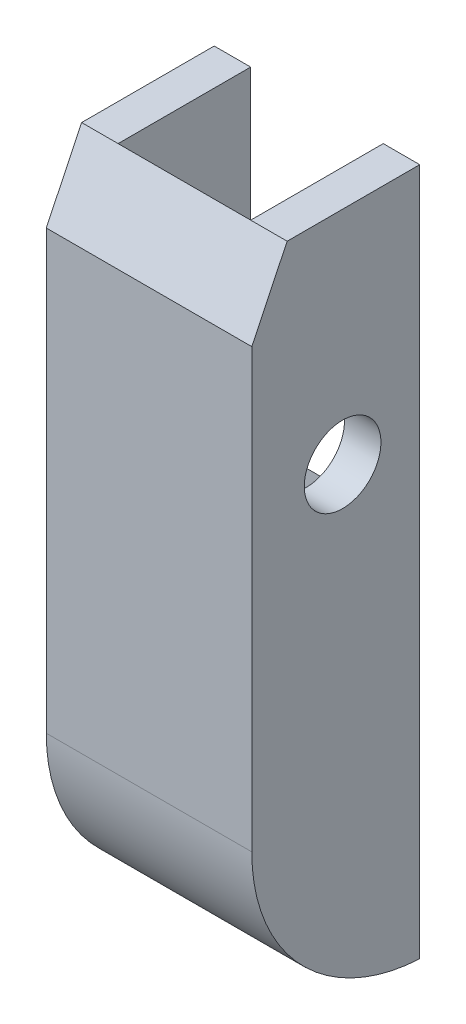
SolidWorks part; units mm, degrees
ref_plane "Front Plane" through (0, 0, 0) normal (0, 0, 1) x (1, 0, 0)
ref_plane "Top Plane" through (0, 0, 0) normal (0, 1, 0) x (1, 0, 0)
ref_plane "Right Plane" through (0, 0, 0) normal (1, 0, 0) x (0, 0, -1)
sketch "Sketch1" plane through (0, 0, 0) normal (0, 0, 1) x (1, 0, 0)
  line L1 (0, 0) -> (11.811, 0)
  line L2 (0, 0) -> (0, 45.9892)
  line L3 (0, 45.9892) -> (11.811, 45.9892)
  line L4 (11.811, 0) -> (11.811, 45.9892)
  dimension "D1" = 11.811
  dimension "D2" = 45.9892
extrude "Boss-Extrude1" add sketch "Sketch1" along normal blind 9.652 contours L2 L3 L4 L1
fillet "Fillet5" radius 4.826 1 edges at (5.9055, 45.9892, 0)
sketch "Sketch2" plane through (0, 0, 0) normal (0, 0, -1) x (-1, 0, 0)
  line L0 (0, 45.9892) -> (-11.811, 45.9892) construction
  line L1 (-9.7155, 45.9892) -> (-2.0955, 45.9892)
  line L2 (-9.7155, 45.9892) -> (-9.7155, 23.6372)
  line L3 (-9.7155, 23.6372) -> (-2.0955, 23.6372)
  line L4 (-2.0955, 45.9892) -> (-2.0955, 23.6372)
  line L5 (0, 0) -> (0, 41.1632) construction
  dimension "D1" = 22.352
  dimension "D2" = 7.62
  dimension "D3" = 2.0955
extrude "Cut-Extrude1" cut sketch "Sketch2" against normal blind 7.62
sketch "Sketch3" plane through (0, 0, 0) normal (-1, 0, 0) x (0, 0, 1)
  line L0 (7.62, 45.9892) -> (7.62, 23.6372) construction
  line L2 (7.62, 23.6372) -> (0, 23.6372) construction
  circle A0 centre (4.4323, 26.8249) radius 2.2035
  dimension "D1" = 3.1877
  dimension "D3" = 4.4069
  dimension "D2" = 3.1877
extrude "Cut-Extrude2" cut sketch "Sketch3" against normal through all and the other way through all
fillet "Fillet4" radius 4.826 1 edges at (5.9055, 45.9892, 9.652)
fillet "Fillet6" radius 10.16 1 edges at (5.9055, 0, 9.652)
sketch "Sketch4" plane through (11.811, 0, 0) normal (1, 0, 0) x (0, 0, -1)
  line L0 (-9.652, 35.2938) -> (-7.62, 39.5249)
  line L1 (-9.652, 10.1473) -> (-9.652, 41.1632) construction
  line L2 (-7.62, 39.5249) -> (0, 39.5249)
  line L3 (0, 0) -> (0, 41.1632) construction
  line L4 (-9.652, 35.2938) -> (-9.652, 45.9892)
  line L5 (-9.652, 45.9892) -> (0, 45.9892)
  line L6 (0, 45.9892) -> (0, 39.5249)
  line L7 (-0.4369, 28.7437) -> (4.2626, 18.9582) construction
  line L8 (-4.4323, 26.8249) -> (0, 26.8249) construction
  line L9 (-4.4323, 26.8249) -> (-0.4369, 28.7437) construction
  line L10 (-4.4323, 26.8249) -> (-0.4369, 24.9061) construction
  arc A0 (-4.826, 45.9892) -> (-9.652, 41.1632) centre (-4.826, 41.1632) ccw construction
  circle A1 centre (7.1247, 20.3327) radius 3.175 construction
  point P14 (-4.4323, 26.8249)
  dimension "D2" = 6.35
  dimension "D1" = 12.7
  dimension "D3" = 11.557
  dimension "D4" = 6.4922
extrude "Cut-Extrude3" cut sketch "Sketch4" against normal through all
sketch "Sketch5" plane through (9.7155, 0, 0) normal (-1, 0, 0) x (0, 0, 1)
  line L0 (5.1581, 23.6372) -> (0, 21.1601)
  line L1 (0, 21.1601) -> (0, 23.6372)
  line L2 (0, 23.6372) -> (5.1581, 23.6372)
  line L3 (4.4323, 26.8249) -> (0.4369, 24.9061) construction
  line L4 (4.4323, 26.8249) -> (7.62, 26.8249) construction
  line L5 (4.4323, 26.8249) -> (5.8123, 23.9514) construction
  line L6 (7.62, 39.5249) -> (7.62, 23.6372) construction
  line L7 (5.8123, 23.9514) -> (5.1581, 23.6372)
  line L8 (7.62, 26.8249) -> (7.62, 23.6372)
  line L9 (7.62, 23.6372) -> (5.1581, 23.6372)
  arc A0 (5.8123, 23.9514) -> (7.62, 26.8249) centre (4.4323, 26.8249) ccw
  line M4 (7.62, 23.6372) -> (7.62, 39.5249)
  line M7 (0, 23.6372) -> (7.62, 23.6372)
extrude "Cut-Extrude4" cut sketch "Sketch5" along normal up to surface (7.62 mm away) contours L1 L0 M7 region at (9.7155, 22.8115, 1.7194) up to face at (2.0955, 24.6215, 4.4323)
extrude "Boss-Extrude2" add sketch "Sketch5<3>" along normal up to surface (7.62 mm away) contours A0 L7 M7 M4 region at (9.7155, 24.361, 6.9399) up to face at (2.0955, 24.6215, 4.4323)
sketch "Sketch5<3>" plane through (9.7155, 0, 0) normal (-1, 0, 0) x (0, 0, 1) same geometry as "Sketch5"
